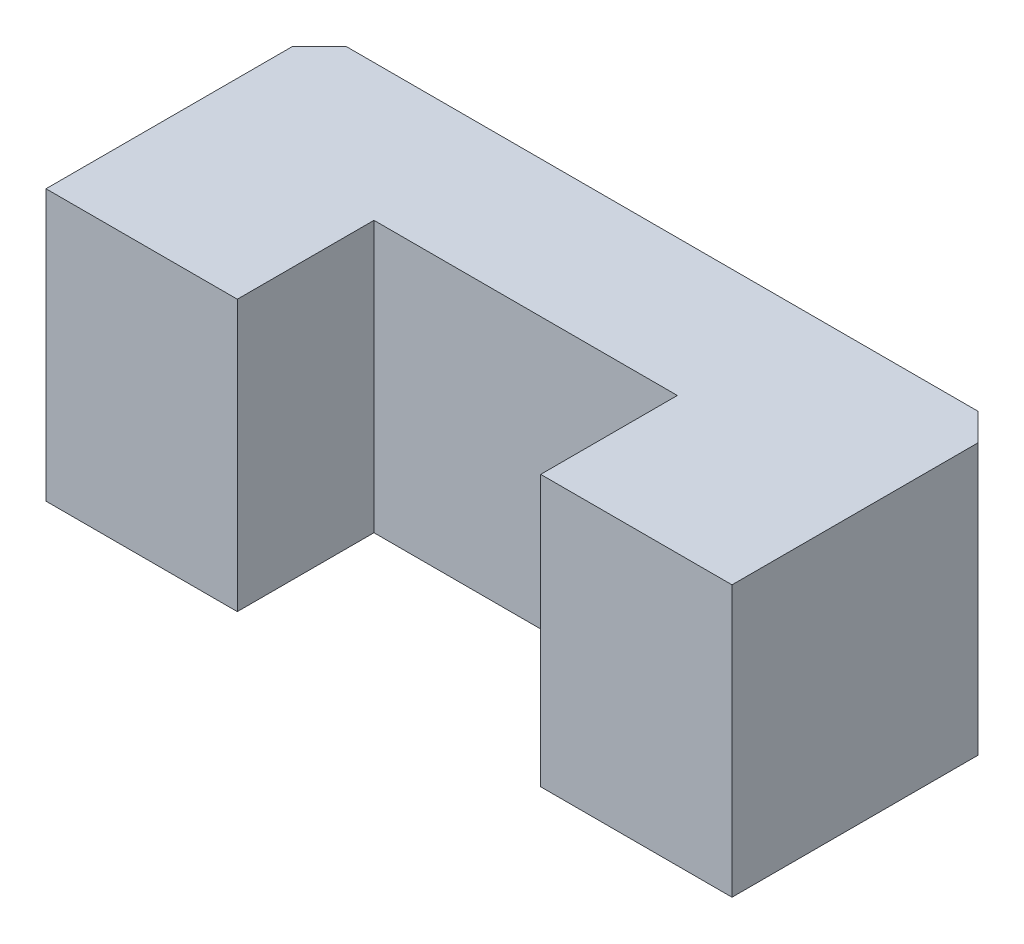
SolidWorks part; units mm, degrees
ref_plane "정면" through (0, 0, 0) normal (0, 0, 1) x (1, 0, 0)
ref_plane "윗면" through (0, 0, 0) normal (0, 1, 0) x (1, 0, 0)
ref_plane "우측면" through (0, 0, 0) normal (1, 0, 0) x (0, 0, -1)
sketch "스케치1" plane through (0, 0, 0) normal (0, 0, 1) x (1, 0, 0)
  line L0 (0, 4.5786) -> (0, -5.0471) construction
  line L1 (-12.55, 4.95) -> (12.55, 4.95)
  line L2 (-12.55, 4.95) -> (-12.55, -4.95)
  line L3 (-12.55, -4.95) -> (12.55, -4.95)
  line L4 (12.55, 4.95) -> (12.55, -4.95)
  line L5 (-12.55, 4.95) -> (12.55, -4.95) construction
  line L6 (-12.55, -4.95) -> (12.55, 4.95) construction
  line L7 (-5.55, 4.95) -> (-5.55, -4.95)
  line L8 (5.55, 4.95) -> (5.55, -4.95)
  point P0 (0, 0)
  dimension "D1" = 7
  dimension "D2" = 11.1
  dimension "D3" = 9.9
extrude "보스-돌출1" add sketch "스케치1" along normal blind 5 contours L8 L1 L7 L3 region at (0, 0, 0)
extrude "보스-돌출2" add sketch "스케치1<3>" along normal blind 10 contours L7 L1 L2 L3 | L1 L8 L3 L4 region at (-9.05, 0, 0) region at (9.05, 0, 0)
sketch "스케치1<3>" plane through (0, 0, 0) normal (0, 0, 1) x (1, 0, 0) same geometry as "스케치1"
chamfer "모따기1" distance 1 angle 45 2 edges at (12.55, 0, 0) (-12.55, 0, 0)
